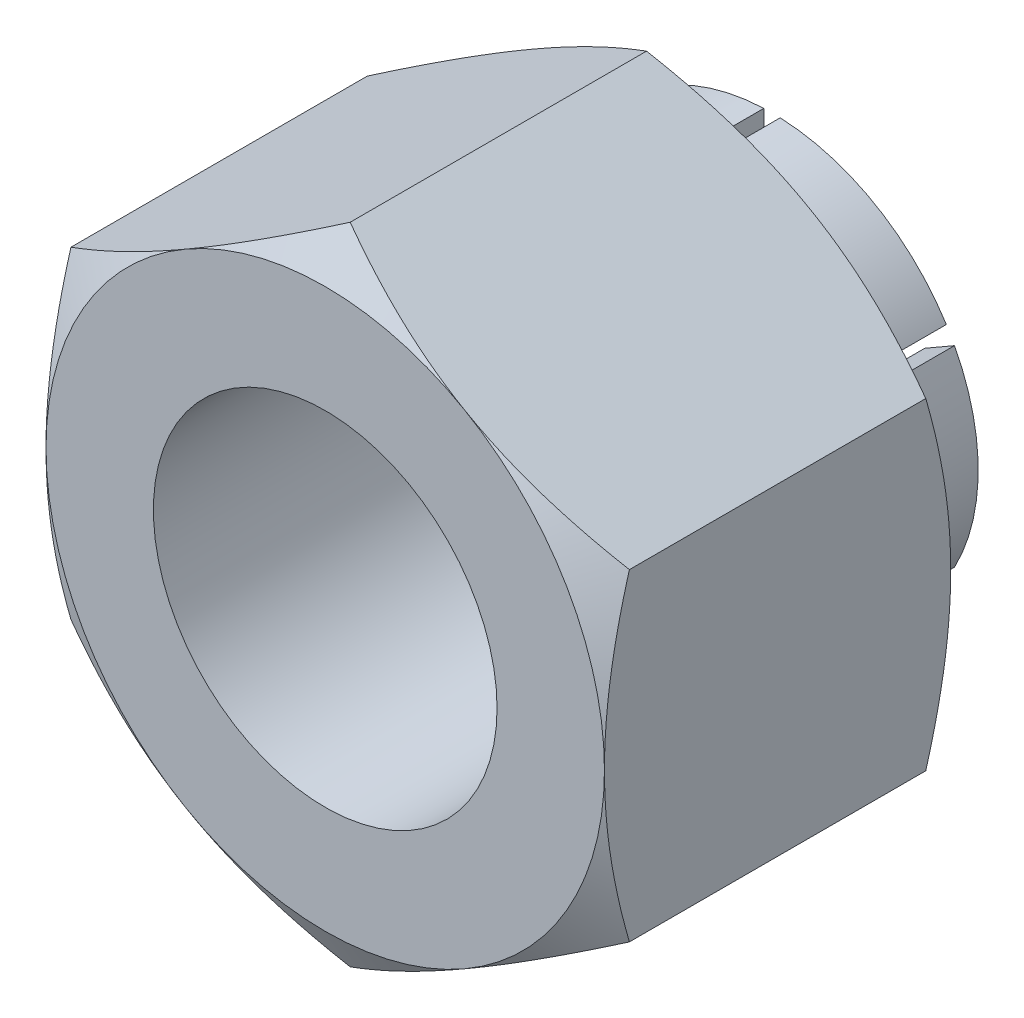
SolidWorks part; units mm, degrees
material "Alloy Steel"
ref_plane "Front Plane" through (0, 0, 0) normal (0, 0, 1) x (1, 0, 0)
ref_plane "Top Plane" through (0, 0, 0) normal (0, 1, 0) x (1, 0, 0)
ref_plane "Right Plane" through (0, 0, 0) normal (1, 0, 0) x (0, 0, -1)
sketch "Sketch1" plane through (0, 0, 0) normal (0, 0, 1) x (1, 0, 0)
  line L1 (0, 7.5056) -> (-6.5, 3.7528)
  line L2 (-6.5, 3.7528) -> (-6.5, -3.7528)
  line L3 (-6.5, -3.7528) -> (0, -7.5056)
  line L4 (0, -7.5056) -> (6.5, -3.7528)
  line L5 (6.5, -3.7528) -> (6.5, 3.7528)
  line L6 (6.5, 3.7528) -> (0, 7.5056)
  circle A0 centre (0, 0) radius 6.5 construction
  dimension "Hex" = 13
extrude "Extrude1" add sketch "Sketch1" against normal blind 10.4
sketch "Sketch2" plane through (0, 0, 0) normal (0, 0, 1) x (1, 0, 0)
  circle A0 centre (0, 0) radius 6.5 construction
  circle A1 centre (0, 0) radius 6.5
extrude "Cut-Extrude1" cut sketch "Sketch2" against normal through all draft 60 flip side to cut
sketch "Sketch4" plane through (0, 0, 0) normal (0, 0, 1) x (1, 0, 0)
  circle A0 centre (0, 0) radius 4
  dimension "Thread Dia" = 8
extrude "Cut-Extrude3" cut sketch "Sketch4" against normal through all
sketch "Sketch7" plane through (0, 0, 0) normal (0, 0, 1) x (1, 0, 0)
  circle A1 centre (0, 0) radius 4
  circle A2 centre (0, 0) radius 4
  dimension "D1" = 0
sketch "Sketch8" plane through (0, 0, -10.4) normal (0, 0, -1) x (-1, 0, 0)
  circle A1 centre (0, 0) radius 4
  circle A3 centre (0, 0) radius 4
  dimension "D1" = 0
sketch "Sketch5" plane through (0, 0, 0) normal (0, 0, 1) x (1, 0, 0)
  circle A0 centre (0, 0) radius 4 construction
  circle A1 centre (0, 0) radius 4
curve "Helix/Spiral1" pitch 1.25 height 11.65 turns 9.32 parameters "pitch"=1.25
sketch "Sketch9" plane through (0, 0, 0) normal (1, 0, 0) x (0, 0, -1)
  line L0 (-0.625, 3.1881) -> (-0.4688, 3.1881)
  line L1 (-0.4688, 3.1881) -> (0, 4)
  line L2 (-0.625, 3.1881) -> (-1.0938, 4)
  line L3 (-1.0938, 4) -> (0, 4)
  line L4 (-0.5469, 3.1881) -> (-0.5469, 4) construction
  line L5 (-0.8594, 3.5941) -> (-0.2344, 3.5941) construction
  line L6 (0, 4) -> (0, -4) construction
  dimension "D1" = 0.1562
  dimension "D2" = 0.625
  dimension "D3" = 60
sweep "Sweep1" [suppressed] add profiles "Sketch9" path "Helix/Spiral1"
sketch "Sketch10" plane through (0, 0, 0) normal (0, 0, 1) x (1, 0, 0)
  line L6 (0, 7.5056) -> (-6.5, 3.7528)
  line L7 (-6.5, 3.7528) -> (-6.5, -3.7528)
  line L8 (-6.5, -3.7528) -> (0, -7.5056)
  line L9 (0, -7.5056) -> (6.5, -3.7528)
  line L10 (6.5, -3.7528) -> (6.5, 3.7528)
  line L11 (6.5, 3.7528) -> (0, 7.5056)
  line L12 (0, 7.5056) -> (-6.5, 3.7528)
  line L13 (-6.5, 3.7528) -> (-6.5, -3.7528)
  line L14 (-6.5, -3.7528) -> (0, -7.5056)
  line L15 (0, -7.5056) -> (6.5, -3.7528)
  line L16 (6.5, -3.7528) -> (6.5, 3.7528)
  line L17 (6.5, 3.7528) -> (0, 7.5056)
  dimension "D1" = 0
extrude "Cut-Extrude8" [suppressed] cut sketch "Sketch10" along normal through all
sketch "Sketch11" plane through (0, 0, -10.4) normal (0, 0, -1) x (-1, 0, 0)
  line L6 (6.5, 3.7528) -> (0, 7.5056)
  line L7 (6.5, -3.7528) -> (6.5, 3.7528)
  line L8 (0, -7.5056) -> (6.5, -3.7528)
  line L9 (-6.5, -3.7528) -> (0, -7.5056)
  line L10 (-6.5, 3.7528) -> (-6.5, -3.7528)
  line L11 (0, 7.5056) -> (-6.5, 3.7528)
  line L12 (6.5, 3.7528) -> (0, 7.5056)
  line L13 (6.5, -3.7528) -> (6.5, 3.7528)
  line L14 (0, -7.5056) -> (6.5, -3.7528)
  line L15 (-6.5, -3.7528) -> (0, -7.5056)
  line L16 (-6.5, 3.7528) -> (-6.5, -3.7528)
  line L17 (0, 7.5056) -> (-6.5, 3.7528)
  dimension "D1" = 0
extrude "Cut-Extrude9" [suppressed] cut sketch "Sketch11" along normal through all
sketch "Sketch12" plane through (0, 0, -10.4) normal (0, 0, -1) x (-1, 0, 0)
  line L0 (0, 0) -> (6.5, 3.7528) construction
  circle A0 centre (0, 0) radius 4.8
  dimension "D1" = 9.6
extrude "Cut-Extrude10" cut sketch "Sketch12" against normal blind 2.34 flip side to cut
sketch "Sketch15" plane through (0, 0, -10.4) normal (0, 0, -1) x (-1, 0, 0)
  line L0 (0, 0) -> (0, -7.5056)
extrude "Cut-Extrude-Thin2" cut sketch "Sketch15" against normal offset from surface (1.832 mm away) 0.508 thin up to face at (0, 0, -8.06) thin type mid plane wall 0.381
pattern_circular "CirPattern1" count 6 over 360 of "Cut-Extrude-Thin2"
sketch "Sketch3" plane through (0, 0, -8.06) normal (0, 0, -1) x (-1, 0, 0)
  circle A1 centre (0, 0) radius 6.5
  circle A2 centre (0, 0) radius 6.5
  dimension "D1" = 0
extrude "Cut-Extrude2" cut sketch "Sketch3" against normal through all draft 60 flip side to cut
extrude "Cut-Extrude6" [suppressed] cut sketch "Sketch7" against normal through all draft 45
extrude "Cut-Extrude7" [suppressed] cut sketch "Sketch8" against normal through all draft 45
equation "\"D2@Sketch9\" = \"pitch@Helix/Spiral1\"*.5"
equation "\"D3@Helix/Spiral1\" = \"pitch@Helix/Spiral1\"+\"Height@Extrude1\""
equation "\"D1@Sketch9\" = \"pitch@Helix/Spiral1\"*.125"
equation "\"D1@Sketch12\" = \"Thread Dia@Sketch4\"*1.2"
equation "\"D1@Cut-Extrude10\" = \"Height@Extrude1\"*.225"
